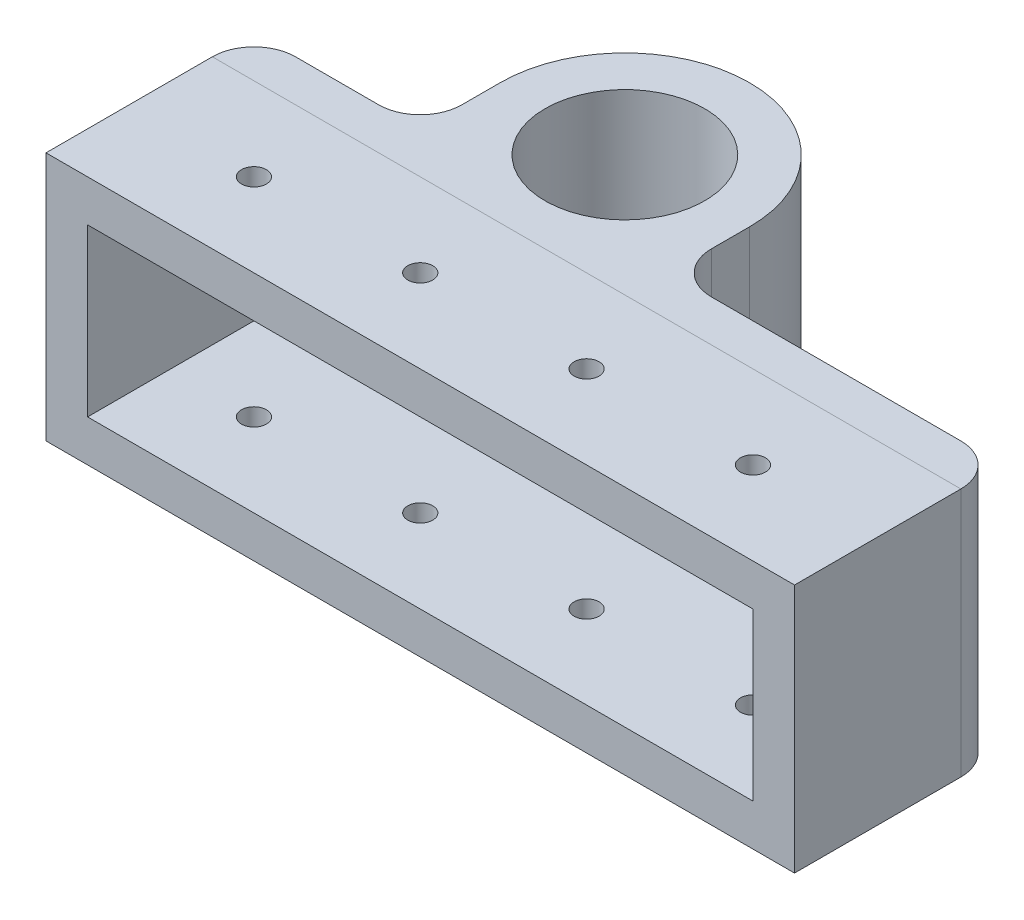
SolidWorks part; units mm, degrees
ref_plane "Plan de face" through (0, 0, 0) normal (0, 0, 1) x (1, 0, 0)
ref_plane "Plan de dessus" through (0, 0, 0) normal (0, 1, 0) x (1, 0, 0)
ref_plane "Plan de droite" through (0, 0, 0) normal (1, 0, 0) x (0, 0, -1)
sketch "Esquisse1" plane through (0, 0, 0) normal (0, 0, 1) x (1, 0, 0)
  line L1 (-40, -10) -> (40, -10)
  line L2 (-40, -10) -> (-40, 10)
  line L3 (-40, 10) -> (40, 10)
  line L4 (40, -10) -> (40, 10)
  line L5 (-40, -10) -> (40, 10) construction
  line L6 (-40, 10) -> (40, -10) construction
  line L7 (45, -15) -> (-45, -15)
  line L8 (45, -15) -> (45, 15)
  line L9 (45, 15) -> (-45, 15)
  line L10 (-45, -15) -> (-45, 15)
  line L11 (45, -15) -> (-45, 15) construction
  line L12 (45, 15) -> (-45, -15) construction
  point P0 (0, 0)
  point P6 (0, 0)
  dimension "D1" = 80
  dimension "D2" = 20
  dimension "D3" = 90
  dimension "D4" = 30
extrude "Boss.-Extru.1" add sketch "Esquisse1" along normal blind 20
sketch "Esquisse2" plane through (0, 15, 0) normal (0, 1, 0) x (1, 0, 0)
  line L0 (-45, 0) -> (45, 0)
  line L1 (-45, 0) -> (-45, 5)
  line L2 (45, 0) -> (45, 5)
  line L3 (-45, 5) -> (45, 5)
  line L4 (-45, 5) -> (-10, 5) construction
  line L5 (-10, 5) -> (-10, 14.6) construction
  line L7 (-25, 29.6) -> (5, 29.6)
  line L8 (-25, 29.6) -> (-25, -0.4)
  line L9 (-25, -0.4) -> (5, -0.4)
  line L10 (5, 29.6) -> (5, -0.4)
  line L11 (-25, 29.6) -> (5, -0.4) construction
  line L12 (-25, -0.4) -> (5, 29.6) construction
  circle A0 centre (-10, 14.6) radius 9.6
  circle A1 centre (-10, 14.6) radius 15
  line M3 (45, 0) -> (-45, 0)
  dimension "D4" = 30
  dimension "D1" = 5
  dimension "D2" = 55
  dimension "D3" = 9.6
sketch "Esquisse3" plane through (0, -15, 0) normal (0, -1, 0) x (1, 0, 0)
  line L0 (-45, 20) -> (45, 20)
  line L1 (-45, 20) -> (-45, 10)
  line L2 (45, 20) -> (45, 10)
  line L3 (-45, 10) -> (45, 10)
  circle A0 centre (-30, 10) radius 1.5
  circle A1 centre (-10, 10) radius 1.5
  circle A2 centre (10, 10) radius 1.5
  circle A3 centre (30, 10) radius 1.5
  dimension "D2" = 3
  dimension "D3" = 3
  dimension "D4" = 3
  dimension "D5" = 3
  dimension "D1" = 10
  dimension "D6" = 15
  dimension "D7" = 20
  dimension "D8" = 15
  dimension "D9" = 20
extrude "Enlèv. mat.-Extru.1" cut sketch "Esquisse3" against normal blind 30 contours L3 A3 | L3 A3 | L3 A2 | L3 A2 | L3 A1 | L3 A1 | L3 A0 | L3 A0
extrude "Boss.-Extru.3" add sketch "Esquisse2" against normal blind 30 separate body contours L8 L3 L1 L0 | A1 L3 L8 L9 | A1 L8 L3 | A1 L3 A0 | L3 A1 | A1 L3 L10 | A1 L0 L10 L3 | L3 L10 L2 M3
fillet "Congé1" radius 5 2 edges at (-25, 0, -5) (5, 0, -5)
fillet "Congé2" radius 5 2 edges at (-45, 0, -5) (45, 0, -5)
